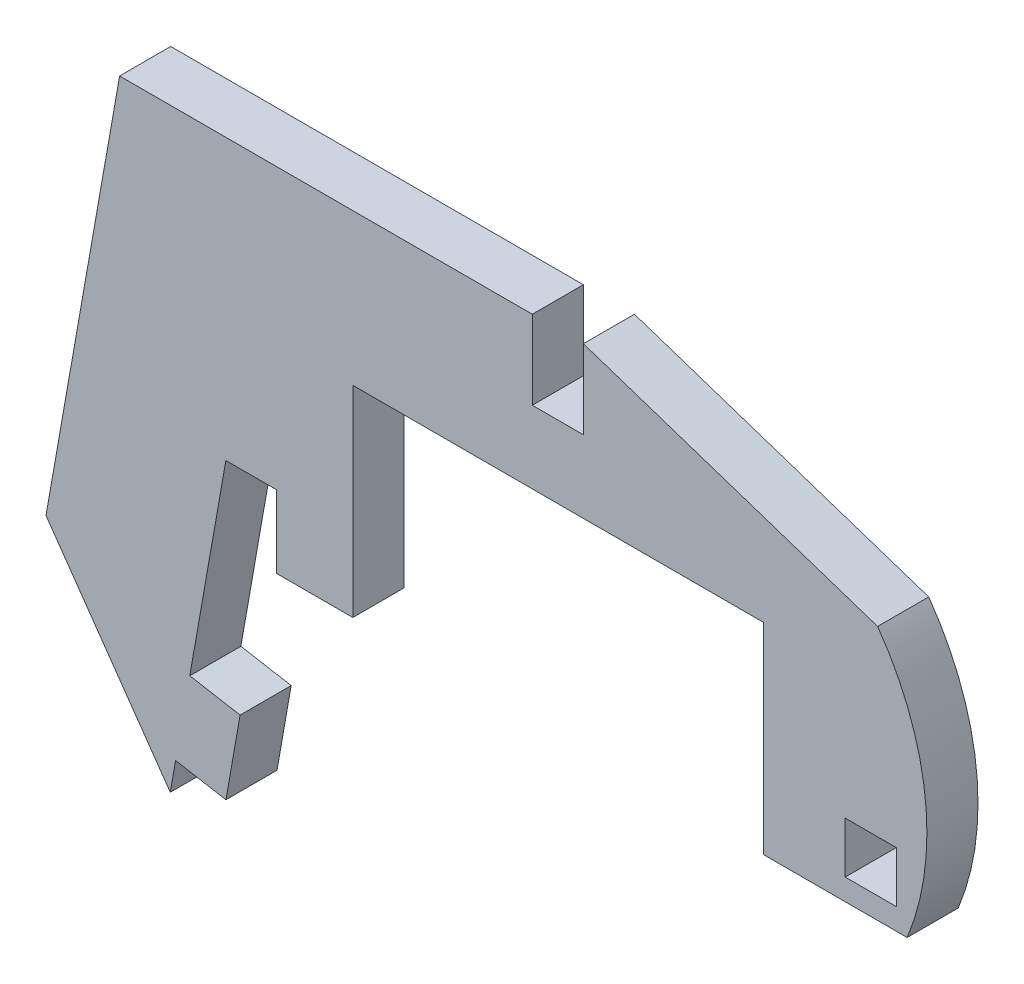
SolidWorks part; units mm, degrees
material "Balsa"
ref_plane "Plan de face" through (0, 0, 0) normal (0, 0, 1) x (1, 0, 0)
ref_plane "Plan de dessus" through (0, 0, 0) normal (0, 1, 0) x (1, 0, 0)
ref_plane "Plan de droite" through (0, 0, 0) normal (1, 0, 0) x (0, 0, -1)
sketch "Esquisse1" plane through (0, 0, 0) normal (0, 0, 1) x (1, 0, 0)
  line L0 (0, 0) -> (0, -19.685)
  line L1 (0, -19.685) -> (20, -19.685)
  line L2 (20, -19.685) -> (20, 2.315)
  line L3 (20, 2.315) -> (-17.6294, 14.8091)
  line L4 (-63.0278, 14.8091) -> (-70.2342, -26.0601)
  line L5 (-17.6294, 14.8091) -> (-63.0278, 14.8091)
  line L6 (-70.2342, -26.0601) -> (-54.011, -49.2292)
  line L7 (-40.2, -19.685) -> (-40.2, 0)
  line L8 (-40.2, 0) -> (0, 0)
  line L10 (-48.8016, -19.685) -> (-40.2, -19.685)
  line L11 (-54.011, -49.2292) -> (-48.8016, -19.685)
  dimension "D1" = 19.685
  dimension "D2" = 40.2
  dimension "D3" = 19.685
  dimension "D4" = 20
  dimension "D5" = 34.4941
  dimension "D6" = 22
  dimension "D7" = 22.5706
  dimension "D8" = 100
  dimension "D9" = 135
  dimension "D10" = 45.3985
  dimension "D11" = 30
  dimension "D12" = 8.6016
extrude "Boss.-Extru.1" add sketch "Esquisse1" along normal blind 5 contours L3 L5 L4 L6 L11 L10 L7 L8 L0 L1 L2
sketch "Esquisse2" plane through (0, 0, 0) normal (0, 0, -1) x (-1, 0, 0)
  line L0 (0, -19.685) -> (-20, -19.685) construction
  line L1 (-20, 2.315) -> (17.6294, 14.8091) construction
  line L2 (-11.1744, 5.2454) -> (-11.9977, 9.9142)
  line L3 (-11.9977, 9.9142) -> (-30.7322, 6.6108)
  line L4 (-30.7322, 6.6108) -> (-25.7328, -21.7423)
  line L5 (-25.7328, -21.7423) -> (-14.065, -19.685)
  line L6 (17.6294, 14.8091) -> (63.0278, 14.8091) construction
  line L7 (-13, -17.5925) -> (-13, -12.5925)
  line L8 (-20, -19.685) -> (-20, 2.315) construction
  line L9 (-13, -17.5925) -> (-8, -17.5925)
  line L10 (-8, -12.5925) -> (-8, -17.5925)
  line L11 (22.6294, 14.8091) -> (17.6294, 14.8091)
  line L12 (-13, -12.5925) -> (-8, -12.5925)
  line L13 (22.6294, 14.8091) -> (22.6294, 7.0925)
  line L14 (22.6294, 7.0925) -> (17.6294, 7.0925)
  line L15 (17.6294, 14.8091) -> (17.6294, 7.0925)
  line L16 (47.693, -34.0964) -> (47.693, -12.5925)
  line L17 (47.693, -12.5925) -> (52.6281, -12.5925)
  line L18 (52.6281, -12.5925) -> (56.1567, -32.6041)
  line L20 (56.1567, -32.6041) -> (47.693, -34.0964)
  line L21 (40.2, -19.685) -> (40.2, 0) construction
  line L25 (48.8016, -19.685) -> (40.2, -19.685) construction
  line L26 (57.5459, -40.4825) -> (58.935, -48.361)
  line L27 (57.5459, -40.4825) -> (52.6218, -41.3508)
  line L28 (58.935, -48.361) -> (54.011, -49.2292)
  line L29 (52.6218, -41.3508) -> (54.011, -49.2292)
  line L30 (70.2342, -26.0601) -> (54.011, -49.2292) construction
  line L31 (54.011, -49.2292) -> (48.8016, -19.685) construction
  arc A1 (-14.065, -19.685) -> (-11.1744, 5.2454) centre (10, -9.8425) cw
  dimension "D4" = 26
  dimension "D1" = 5
  dimension "D2" = 2.0925
  dimension "D3" = 12
  dimension "D5" = 5
  dimension "D6" = 100
  dimension "D7" = 36.3203
  dimension "D8" = 4.9351
  dimension "D9" = 7.493
  dimension "D10" = 7.0925
  dimension "D11" = 8
  dimension "D12" = 8
extrude "Enlèv. mat.-Extru.1" cut sketch "Esquisse2" against normal blind 5
